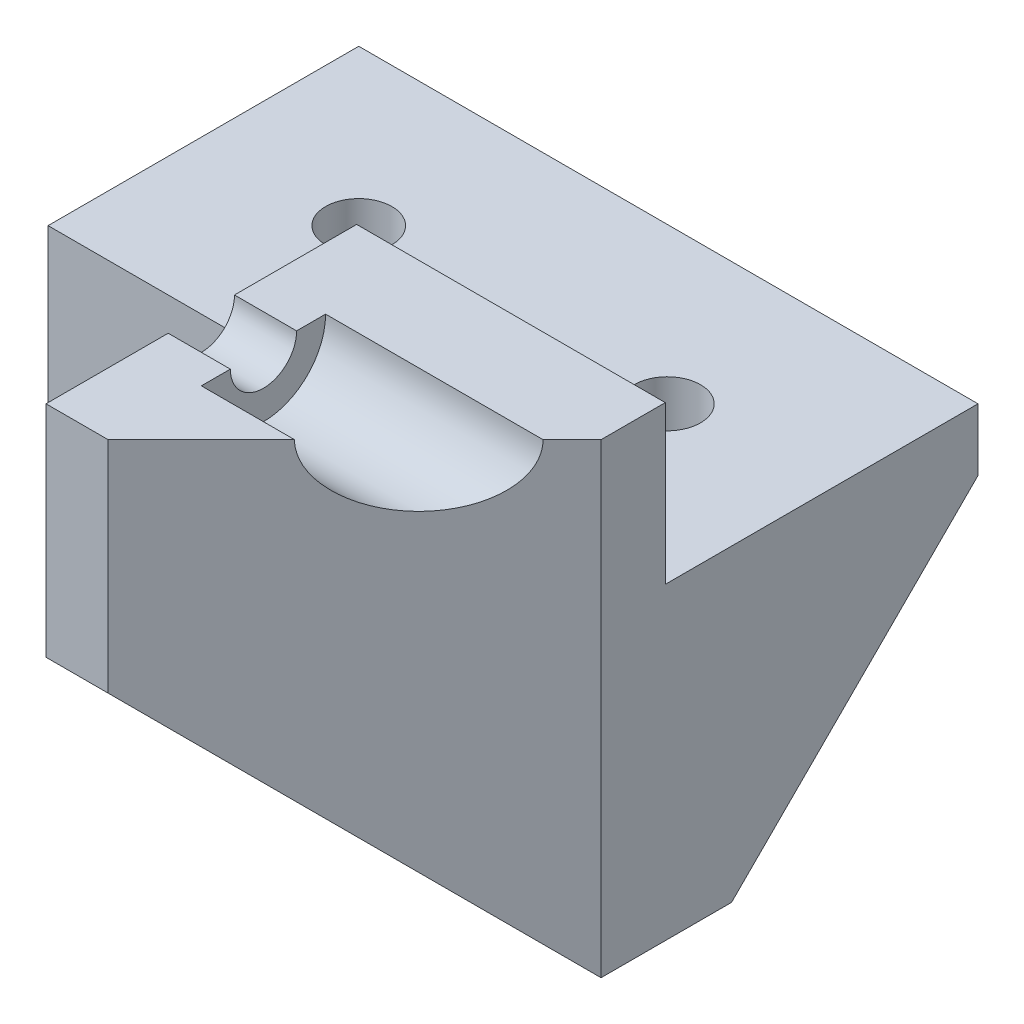
SolidWorks part; units mm, degrees
ref_plane "Front Plane" through (0, 0, 0) normal (1, 0, 0) x (0, 1, 0)
ref_plane "Top Plane" through (0, 0, 0) normal (0, 0, 1) x (0, 1, 0)
ref_plane "Right Plane" through (0, 0, 0) normal (0, 1, 0) x (-1, 0, 0)
sketch "Sketch1" plane through (0, 0, 0) normal (1, 0, 0) x (0, 1, 0)
  line L0 (0, 0) -> (-15.2, 0)
  line L1 (-15.2, 0) -> (-15.2, -30.2)
  line L2 (-15.2, -30.2) -> (-21.2, -30.2)
  line L3 (-21.2, -30.2) -> (-45, -6.4)
  line L4 (-45, -6.4) -> (-45, 30)
  line L5 (-45, 30) -> (0, 30)
  line L6 (0, 30) -> (0, 0)
  line L7 (-15.2, -0.2) -> (-45, -0.2)
  line L8 (-45, 6.2) -> (-21.2, 30)
  circle A0 centre (0, 15) radius 3.2
  circle A1 centre (-30, 15) radius 3.2 construction
  circle A2 centre (-30, 15) radius 6 construction
  circle A3 centre (0, 15) radius 6
  point P18 (0, 0)
  point P19 (0, 0)
  dimension "D7" = 6.4
  dimension "D8" = 12
  dimension "D1" = 30
  dimension "D2" = 15.2
  dimension "D3" = 29.8
  dimension "D4" = 30.2
  dimension "D5" = 6
  dimension "D6" = 45
  dimension "D9" = 15
  dimension "D10" = 15
  dimension "D11" = 30.2
  dimension "D12" = 45
extrude "Boss-Extrude1" add sketch "Sketch1" along normal blind 29.8 contours A3 L6 L5 L4 L3 L2 L1 L0 A2 | A2 A1 | L6 A3 A0 | L1 L7 L4 L3 L2 region at (0, -19.5951, 12.9419) region at (0, -5.8658, 15) region at (0, -26.8695, -11.9232)
extrude "Boss-Extrude2" add sketch "Sketch1<3>" against normal blind 30 contours L1 L7 L4 L3 L2 region at (0, -26.8695, -11.9232)
sketch "Sketch1<3>" plane through (0, 0, 0) normal (1, 0, 0) x (0, 1, 0) same geometry as "Sketch1"
sketch "Sketch2" plane through (0, 0, 0) normal (0, 1, 0) x (-1, 0, 0)
  line L0 (0, -0.2) -> (0, 0) construction
  line L1 (0, 0) -> (-29.8, 0) construction
  line L2 (-29.8, 0) -> (-29.8, -30.2) construction
  line L3 (-29.8, -30.2) -> (30, -30.2) construction
  line L4 (30, -30.2) -> (30, -0.2) construction
  line L5 (30, -0.2) -> (0, -0.2) construction
  line L6 (0, 0) -> (0, 11.8) construction
  line L7 (0, 11.8) -> (-29.8, 11.8) construction
  line L8 (-29.8, 11.8) -> (-29.8, 0) construction
  line L9 (-29.8, 0) -> (0, 0) construction
  line L10 (0, 18.2) -> (0, 30) construction
  line L11 (0, 30) -> (-29.8, 30) construction
  line L12 (-29.8, 30) -> (-29.8, 18.2) construction
  line L13 (-29.8, 18.2) -> (0, 18.2) construction
  line L14 (0, -0.2) -> (0, 0)
  line L15 (0, 0) -> (-29.8, 0)
  line L16 (-29.8, 0) -> (-29.8, -30.2)
  line L17 (-29.8, -30.2) -> (30, -30.2)
  line L18 (30, -30.2) -> (30, -0.2)
  line L19 (30, -0.2) -> (0, -0.2)
  line L20 (0, 0) -> (0, 11.8)
  line L21 (0, 11.8) -> (-29.8, 11.8)
  line L22 (-29.8, 11.8) -> (-29.8, 0)
  line L23 (-29.8, 0) -> (0, 0)
  line L24 (0, 18.2) -> (0, 30)
  line L25 (0, 30) -> (-29.8, 30)
  line L26 (-29.8, 30) -> (-29.8, 18.2)
  line L27 (-29.8, 18.2) -> (0, 18.2)
  line L28 (-29.8, -6.4) -> (-29.8, 6.2) construction
  line L29 (-29.8, -6.4) -> (-29.8, 6.2)
  line L30 (-29.8, 18.2) -> (-29.8, 11.8) construction
  line L31 (-29.8, 6.2) -> (-6, 30)
  line L32 (-29.8, 18.2) -> (-29.8, 11.8)
  circle A0 centre (-14.8, -15.2) radius 3.2
  circle A1 centre (15, -15.2) radius 3.2
  circle A2 centre (15, -15.2) radius 6
  circle A3 centre (-14.8, -15.2) radius 6
  point P21 (0, 0)
  line M15 (-29.8, 11.8) -> (-29.8, 0)
  dimension "D2" = 6.4
  dimension "D3" = 12
  dimension "D1" = 45
  dimension "D4" = 15
  dimension "D5" = 15
  dimension "D6" = 15
  dimension "D7" = 15
extrude "Cut-Extrude1" cut sketch "Sketch2" against normal through all contours L27 L31 L25 L26 | L27 L32 L21 L31 | L31 L21 M15 | A0 | A1 region at (27.9333, 0, 9.9333) region at (25.2061, 0, 15.3879) region at (20.5259, 0, 24.7482) region at (14.8, 0, -15.2) region at (-15, 0, -15.2)
ref_plane "Plane1" through (0, -21.2, 0) normal (0, 1, 0) x (1, 0, 0)
extrude "Cut-Extrude2" cut sketch "Sketch2<3>" against normal through all from surface contours A3 A0 | A2 A1 region at (-9.1697, 0, -15.2) region at (20.6303, 0, -15.2) starting at plane "Plane1"
sketch "Sketch2<3>" plane through (0, 0, 0) normal (0, 1, 0) x (-1, 0, 0) same geometry as "Sketch2"
extrude "Cut-Extrude3" cut sketch "Sketch1<4>" along normal through all from offset 6 contours L6 A3 A0 region at (0, -5.8658, 15)
sketch "Sketch1<4>" plane through (0, 0, 0) normal (1, 0, 0) x (0, 1, 0) same geometry as "Sketch1"
equation "\"D12@Sketch1\"=\"D6@Sketch1\""
equation "\"D6@Sketch2\"=\"D5@Sketch2\""
equation "\"D7@Sketch2\"=\"D4@Sketch2\""
